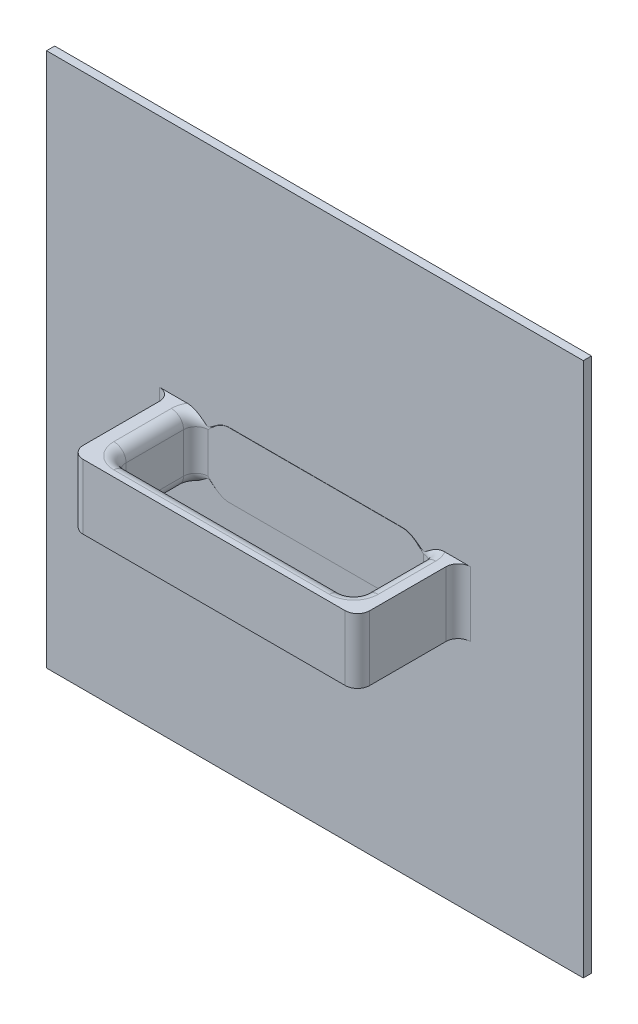
SolidWorks part; units mm, degrees
ref_plane "Front Plane" through (0, 0, 0) normal (0, 0, 1) x (1, 0, 0)
ref_plane "Top Plane" through (0, 0, 0) normal (0, 1, 0) x (1, 0, 0)
ref_plane "Right Plane" through (0, 0, 0) normal (1, 0, 0) x (0, 0, -1)
ref_plane "Plane1" through (0, 0, 333) normal (0, 0, 1) x (1, 0, 0)
sketch "Sketch1" plane through (0, 0, 333) normal (0, 0, 1) x (1, 0, 0)
  line L0 (98.6419, 98.2532) -> (-98.6419, 98.2532)
  line L1 (-98.6419, 98.2532) -> (-98.6419, -98.2532)
  line L2 (-98.6419, -98.2532) -> (98.6419, -98.2532)
  line L3 (98.6419, -98.2532) -> (98.6419, 98.2532)
extrude "Boss-Extrude1" add sketch "Sketch1" against normal blind 3
sketch "Sketch2" plane through (0, 0, 333) normal (0, 0, 1) x (1, 0, 0)
  line L0 (52.6471, 11.9091) -> (52.6471, -11.9091)
  line L1 (52.6471, -11.9091) -> (-52.6471, -11.9091)
  line L2 (-52.6471, -11.9091) -> (-52.6471, 11.9091)
  line L3 (-52.6471, 11.9091) -> (52.6471, 11.9091)
extrude "Boss-Extrude2" add sketch "Sketch2" along normal blind 37
sketch "Sketch3" plane through (0, 11.9091, 0) normal (0, 1, 0) x (-1, 0, 0)
  line L0 (43.6951, 363.2094) -> (-44.4889, 363.2094)
  line L1 (-44.4889, 363.2094) -> (-44.4889, 333.0846)
  line L2 (-44.4889, 333.0846) -> (43.6951, 333.0846)
  line L3 (43.6951, 333.0846) -> (43.6951, 363.2094)
extrude "Cut-Extrude1" cut sketch "Sketch3" against normal through all
sketch "Sketch4" plane through (0, 0, 330) normal (0, 0, -1) x (-1, 0, 0)
  line L0 (88.6419, 88.2532) -> (88.6419, -88.2532)
  line L1 (88.6419, -88.2532) -> (-88.6419, -88.2532)
  line L2 (-88.6419, -88.2532) -> (-88.6419, 88.2532)
  line L3 (-88.6419, 88.2532) -> (88.6419, 88.2532)
extrude "Boss-Extrude3" add sketch "Sketch4" along normal blind 3
fillet "Fillet1" radius 4.5 14 edges at (44.4889, 11.9091, 348.147) (0.3969, 11.9091, 363.2094) (-43.6951, 11.9091, 348.147) (-52.6471, 0, 333) (-43.6951, -11.9091, 348.147) (44.4889, -11.9091, 348.147) (0.3969, -11.9091, 363.2094) (44.4889, 0, 363.2094) (52.6471, 0, 333) (52.6471, 0, 370) (-43.6951, 0, 333.0846) (-43.6951, 0, 363.2094) (-52.6471, 0, 370) (44.4889, 0, 333.0846) tangent propagation no
